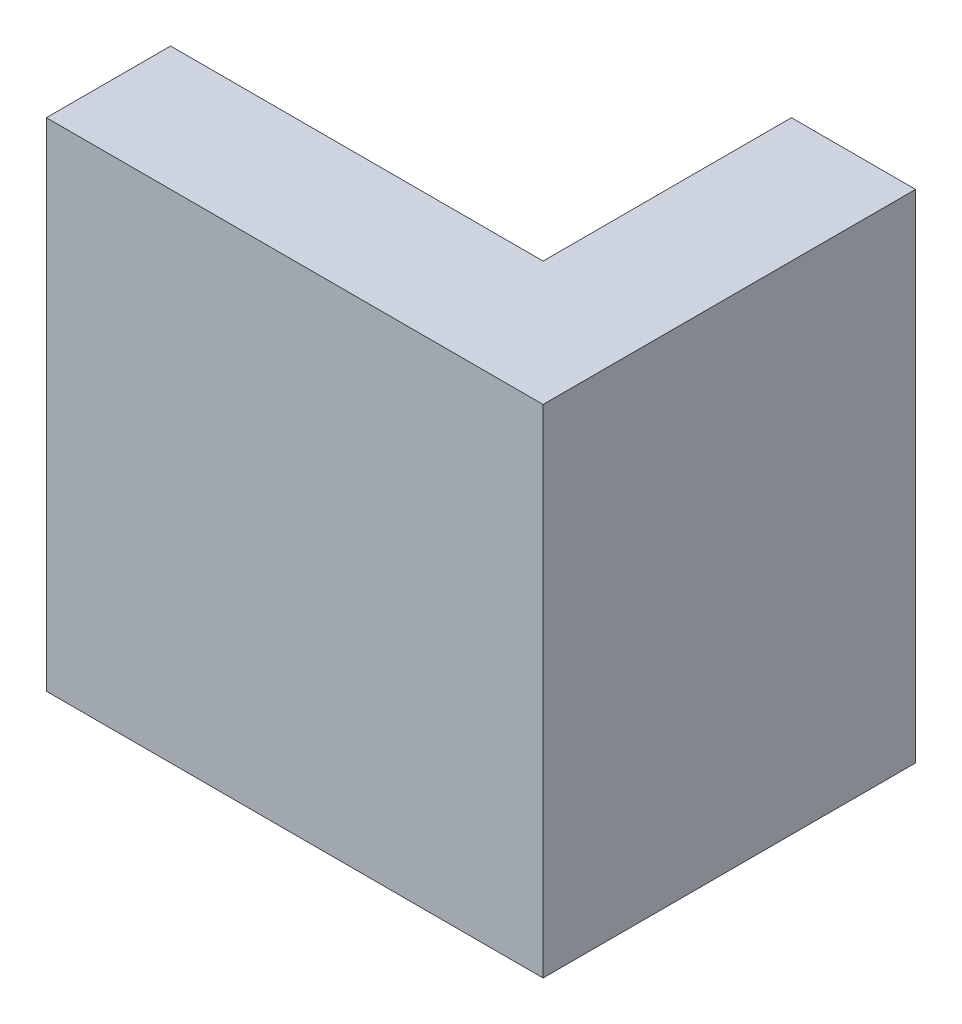
SolidWorks part; units mm, degrees
material "Acrylic (Medium-high impact)"
ref_plane "Front Plane" through (0, 0, 0) normal (0, 0, 1) x (1, 0, 0)
ref_plane "Top Plane" through (0, 0, 0) normal (0, 1, 0) x (1, 0, 0)
ref_plane "Right Plane" through (0, 0, 0) normal (1, 0, 0) x (0, 0, -1)
sketch "Sketch1" plane through (0, 0, 0) normal (0, 1, 0) x (1, 0, 0)
  line L1 (0, 0) -> (12.7, 0)
  line L2 (0, 0) -> (0, 3.175)
  line L3 (0, 3.175) -> (12.7, 3.175)
  line L4 (12.7, 0) -> (12.7, 3.175)
  dimension "D1" = 12.7
  dimension "D2" = 3.175
extrude "Boss-Extrude1" add sketch "Sketch1" along normal blind 12.7
sketch "Sketch2" plane through (0, 0, -3.175) normal (0, 0, -1) x (-1, 0, 0)
  line L5 (-12.7, 0) -> (0, 0) construction
  line L6 (-12.7, 12.7) -> (-9.525, 12.7)
  line L7 (-12.7, 12.7) -> (-12.7, 0)
  line L8 (-12.7, 0) -> (-9.525, 0)
  line L9 (-9.525, 12.7) -> (-9.525, 0)
  dimension "D1" = 3.175
extrude "Boss-Extrude2" add sketch "Sketch2" along normal blind 6.35
